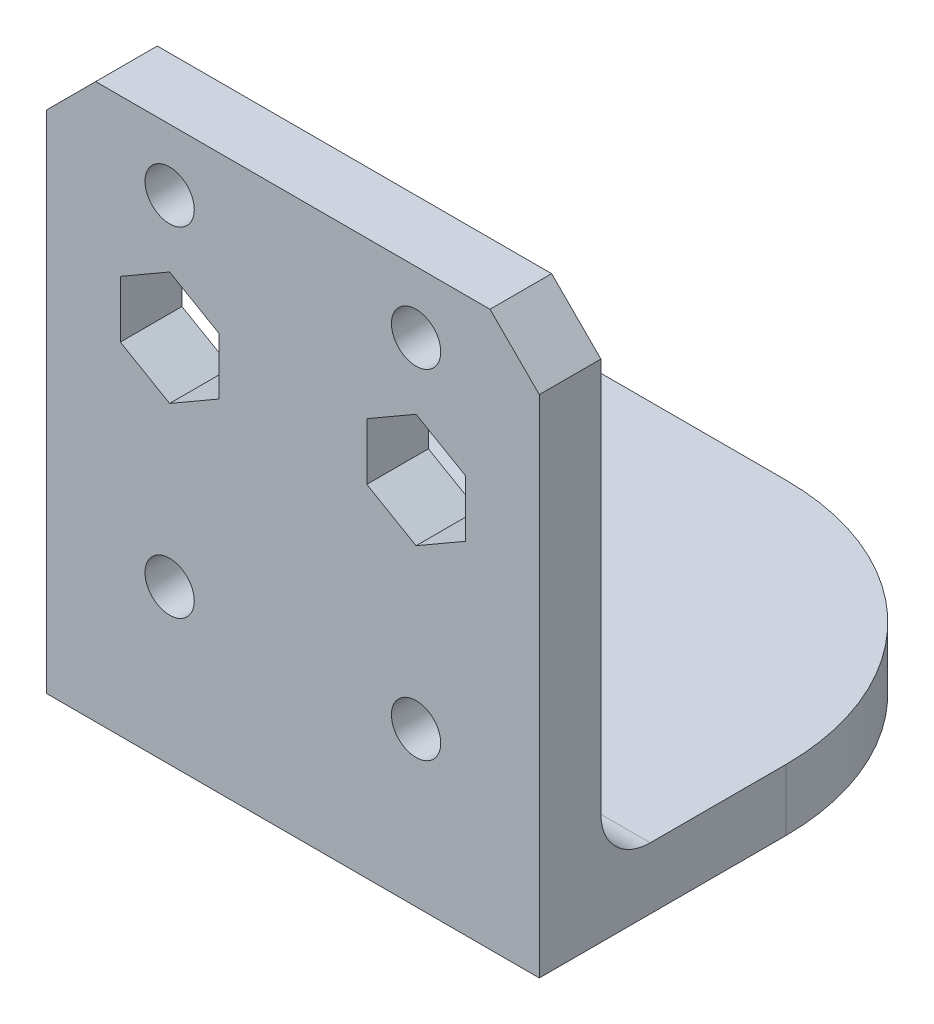
SolidWorks part; units mm, degrees
ref_plane "Front Plane" through (0, 0, 0) normal (0, 0, 1) x (1, 0, 0)
ref_plane "Top Plane" through (0, 0, 0) normal (0, 1, 0) x (1, 0, 0)
ref_plane "Right Plane" through (0, 0, 0) normal (1, 0, 0) x (0, 0, -1)
sketch "Sketch1" plane through (0, 0, 0) normal (1, 0, 0) x (0, 0, -1)
  line L0 (0, 0) -> (0, 57.15)
  line L1 (0, 57.15) -> (6.35, 57.15)
  line L2 (6.35, 57.15) -> (6.35, 6.35)
  line L3 (6.35, 6.35) -> (50.8, 6.35)
  line L4 (50.8, 6.35) -> (50.8, 0)
  line L5 (50.8, 0) -> (0, 0)
  dimension "D1" = 57.15
  dimension "D2" = 6.35
  dimension "D3" = 50.8
extrude "Boss-Extrude1" add sketch "Sketch1" along normal blind 50.8
sketch "Sketch2" plane through (0, 0, 0) normal (0, 0, 1) x (1, 0, 0)
  line L0 (33.02, 41.0329) -> (38.1, 43.9659)
  line L1 (17.78, 41.0329) -> (12.7, 43.9659)
  line L2 (50.8, 0) -> (0, 0) construction
  line L3 (12.7, 43.9659) -> (7.62, 41.0329)
  line L4 (25.4, 0) -> (25.4, 57.15) construction
  line L5 (50.8, 57.15) -> (0, 57.15) construction
  line L6 (7.62, 41.0329) -> (7.62, 35.1671)
  line L7 (7.62, 35.1671) -> (12.7, 32.2341)
  line L8 (12.7, 32.2341) -> (17.78, 35.1671)
  line L9 (17.78, 35.1671) -> (17.78, 41.0329)
  line L10 (33.02, 35.1671) -> (33.02, 41.0329)
  line L11 (38.1, 32.2341) -> (33.02, 35.1671)
  line L12 (43.18, 35.1671) -> (38.1, 32.2341)
  line L13 (43.18, 41.0329) -> (43.18, 35.1671)
  line L14 (38.1, 43.9659) -> (43.18, 41.0329)
  circle A1 centre (12.7, 15.875) radius 2.54
  circle A6 centre (12.7, 50.8) radius 2.54
  circle A10 centre (12.7, 38.1) radius 5.08 construction
  circle A11 centre (38.1, 15.875) radius 2.54
  circle A12 centre (38.1, 50.8) radius 2.54
  dimension "D2" = 12.7
  dimension "D3" = 12.7
  dimension "D4" = 15.875
  dimension "D5" = 22.225
  dimension "D6" = 10.16
extrude "Cut-Extrude1" cut sketch "Sketch2" against normal through all
sketch "Sketch3" plane through (0, 0, 0) normal (0, -1, 0) x (1, 0, 0)
  line L3 (0, 0) -> (0, -50.8) construction
  line L4 (50.8, 0) -> (0, 0) construction
  circle A1 centre (15.494, -15.875) radius 1.0922
  circle A2 centre (5.08, -38.0746) radius 1.0922
  dimension "D1" = 2.1844
  dimension "D2" = 10.414
  dimension "D3" = 22.1996
  dimension "D4" = 15.875
  dimension "D5" = 5.08
extrude "Cut-Extrude2" cut sketch "Sketch3" against normal through all
fillet "Fillet1" radius 5.08 1 edges at (25.4, 6.35, -6.35)
chamfer "Chamfer1" distance 5.08 angle 45 3 edges at (50.8, 57.15, -3.175) (0, 57.15, -3.175) (0, 3.175, -50.8)
fillet "Fillet2" radius 25.4 1 edges at (50.8, 3.175, -50.8)
